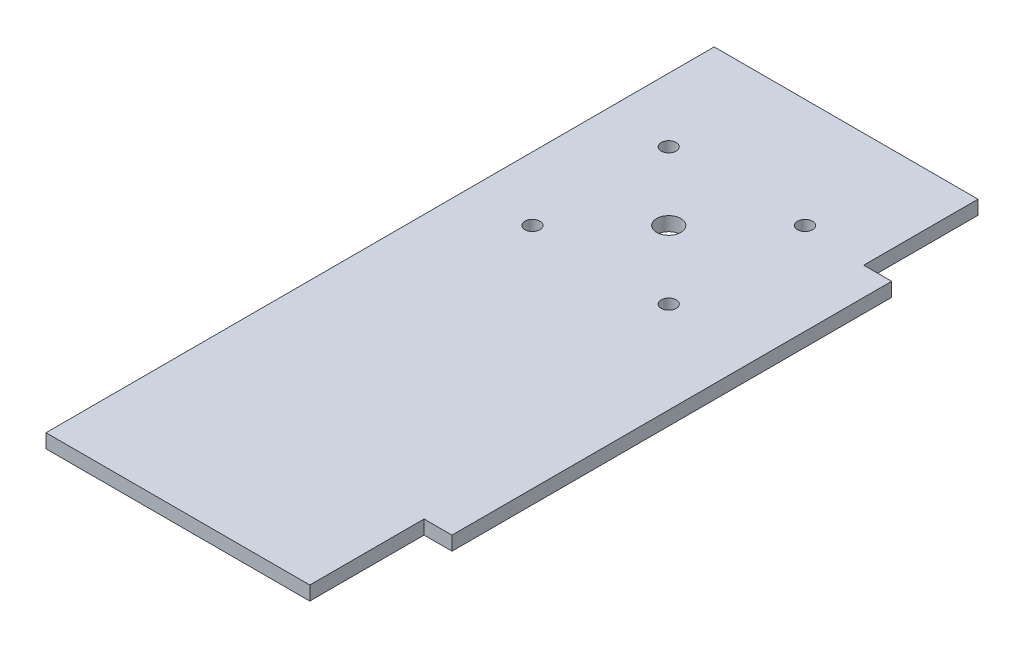
SolidWorks part; units mm, degrees
material "Cedar"
ref_plane "Front Plane" through (0, 0, 0) normal (0, 0, 1) x (1, 0, 0)
ref_plane "Top Plane" through (0, 0, 0) normal (0, 1, 0) x (1, 0, 0)
ref_plane "Right Plane" through (0, 0, 0) normal (1, 0, 0) x (0, 0, -1)
sketch "Sketch1" plane through (0, 0, 0) normal (0, 1, 0) x (1, 0, 0)
  line L0 (-30, 26) -> (30, 26)
  line L1 (30, 26) -> (30, 0)
  line L2 (30, 0) -> (36.35, 0)
  line L3 (36.35, 0) -> (36.35, -100)
  line L4 (36.35, -100) -> (30, -100)
  line L5 (30, -100) -> (30, -126)
  line L6 (30, -126) -> (-30, -126)
  line L7 (-30, -126) -> (-30, -100)
  line L8 (-30, -100) -> (-36.35, -100)
  line L9 (-36.35, -100) -> (-36.35, 0)
  line L10 (-36.35, 0) -> (-30, 0)
  line L11 (-30, 0) -> (-30, 26)
  line L12 (-30, 0) -> (-30, -100) construction
  point P11 (0, 26)
  point P14 (-36.35, -50)
  dimension "D1" = 6.35
  dimension "D2" = 100
  dimension "D3" = 60
  dimension "D4" = 152
extrude "Boss-Extrude1" add sketch "Sketch1" along normal blind 3.175 contours L11 L12 L7 L6 L5 L4 L3 L2 L1 L0 region at (2.1595, 0, 50)
sketch "Sketch2" plane through (0, 3.175, 0) normal (0, 1, 0) x (1, 0, 0)
  line L0 (30, -126) -> (-30, -126) construction
  line L1 (10, -4.35) -> (-10, -4.35) construction
  line L2 (10, -4.35) -> (10, -24.35) construction
  line L3 (10, -24.35) -> (-10, -24.35) construction
  line L4 (-10, -4.35) -> (-10, -24.35) construction
  line L5 (0, 10.15) -> (0, -38.85) construction
  line L6 (-15.5, 1.15) -> (15.5, 1.15) construction
  line L7 (15.5, 1.15) -> (15.5, -29.85) construction
  circle A0 centre (0, -14.35) radius 2.75
  point P4 (0, -18)
  point P5 (0, -24.35)
  point P9 (0, 10.15)
  point P10 (0, -38.85)
  point P13 (10, -14.35)
  point P14 (0, -14.35)
  point P15 (15.5, 1.15)
  point P16 (-15.5, 1.15)
  point P17 (15.5, -29.85)
  point P18 (-15.5, -29.85)
  point P21 (0, 1.15)
  point P22 (15.5, -14.35)
  dimension "D6" = 5.5
  dimension "D1" = 108
  dimension "D2" = 20
  dimension "D4" = 6.35
  dimension "D5" = 49
  dimension "D3" = 31
extrude "Cut-Extrude1" cut sketch "Sketch2" against normal through all
hole_wizard "M3 Clearance Hole1" positions "Sketch6" profile "Sketch5" hole size "M3" standard "ANSI Metric" end condition through all
sketch "Sketch6" plane through (0, 3.175, 0) normal (0, 1, 0) x (1, 0, 0)
  point P6 (-15.5, 1.15)
  point P9 (15.5, 1.15)
  point P12 (15.5, -29.85)
  point P15 (-15.5, -29.85)
sketch "Sketch5" plane through (-15.5, 3.175, -1.15) normal (1, 0, 0) x (0, 0, 1)
  line L0 (0, 0) -> (0, 3.175)
  line L1 (0, 3.175) -> (1.7, 3.175)
  line L2 (1.7, 3.175) -> (1.7, 0)
  line L5 (1.7, 0) -> (0, 0)
  line L11 (0, -6.35) -> (0, 107.95) construction
  dimension "Thru Hole Dia." = 3.4
  dimension "Thru Hole Depth" = 3.175
equation "\"length\"= 152mm"
equation "\"w_mach\" = 60mm"
equation "\"w_tab\"= 100mm"
equation "\"t_wood\"= 0.125in"
equation "\"t_side\"= 0.25in"
equation "\"D1@Sketch1\"=\"t_side\""
equation "\"D2@Sketch1\"=\"w_tab\""
equation "\"D3@Sketch1\"=\"w_mach\""
equation "\"D4@Sketch1\"=\"length\""
equation "\"D1@Boss-Extrude1\"=\"t_wood\""
equation "\"dX\"= 123mm"
equation "\"in_rad\"= 15mm"
equation "\"D1@Sketch2\"=\"dX\"-\"in_rad\""
equation "\"l_motor\"= 20mm"
equation "\"l_servo\"= 40mm"
equation "\"servocenter\"= 6.35mm"
equation "\"D2@Sketch2\"=\"l_motor\""
equation "\"D3@Sketch2\"=31"
equation "\"D4@Sketch2\"=\"servocenter\""
equation "\"servoholes\"= 49mm"
equation "\"D5@Sketch2\"=\"servoholes\""
